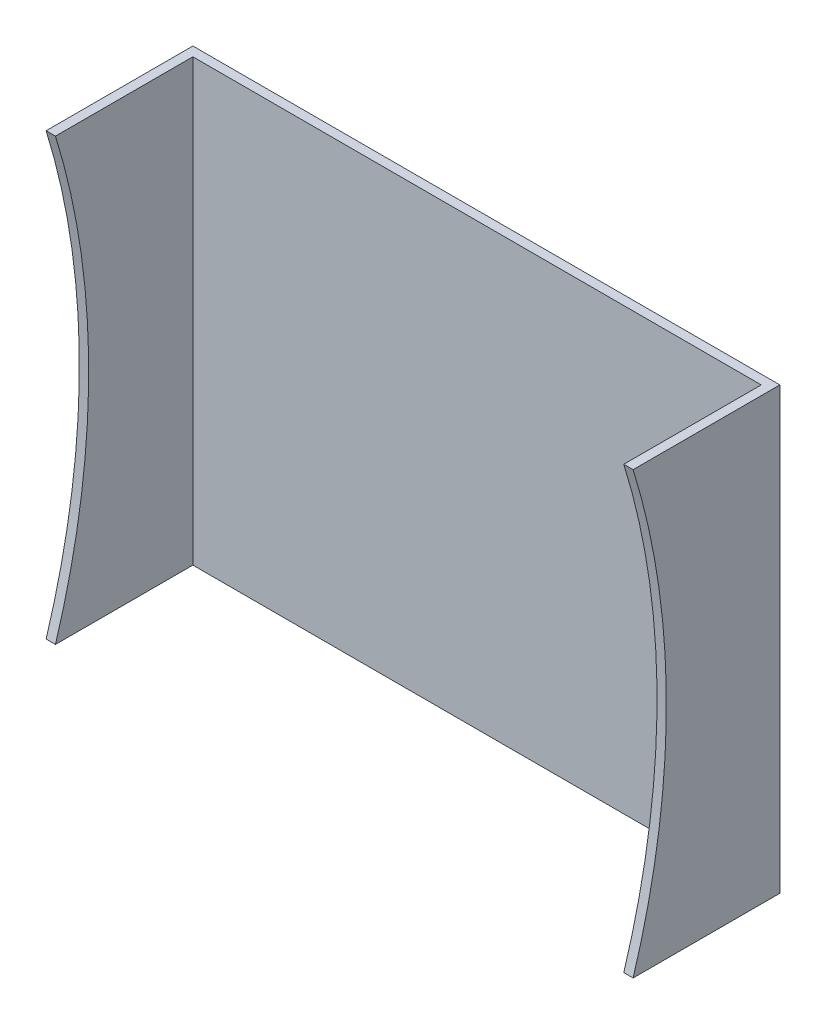
SolidWorks part; units mm, degrees
ref_plane "Front Plane" through (0, 0, 0) normal (0, 0, 1) x (1, 0, 0)
ref_plane "Top Plane" through (0, 0, 0) normal (0, 1, 0) x (1, 0, 0)
ref_plane "Right Plane" through (0, 0, 0) normal (1, 0, 0) x (0, 0, -1)
sketch "Sketch1" plane through (0, 0, 0) normal (1, 0, 0) x (0, 0, -1)
  line L0 (242.6747, 75) -> (292.6747, 75)
  line L1 (292.6747, 75) -> (292.6747, -75)
  line L2 (292.6747, -75) -> (242.6747, -75)
  line L3 (0, 0) -> (562.0527, 0) construction
  line L4 (289.4947, 75) -> (289.4947, -75)
  arc A0 (242.6747, -75) -> (242.6747, 75) centre (0, 0) ccw
  dimension "D1" = 508
  dimension "D2" = 150
  dimension "D3" = 50
  dimension "D4" = 3.18
extrude "Boss-Extrude3" add sketch "Sketch1" along normal blind 3.18 contours A0 L3 L4 L0 | L3 A0 L2 L4 region at (0, 39.2957, -269.7326) region at (0, -39.2957, -269.7326)
extrude "Boss-Extrude4" add sketch "Sketch1<5>" along normal blind 100 contours L4 L3 L1 L0 | L3 L4 L2 L1 region at (0, 37.5, -291.0847) region at (0, -37.5, -291.0847)
sketch "Sketch1<5>" plane through (0, 0, 0) normal (1, 0, 0) x (0, 0, -1) same geometry as "Sketch1"
mirror "Mirror2" about plane through (100, 0, 0) normal (1, 0, 0) of bodies 104
